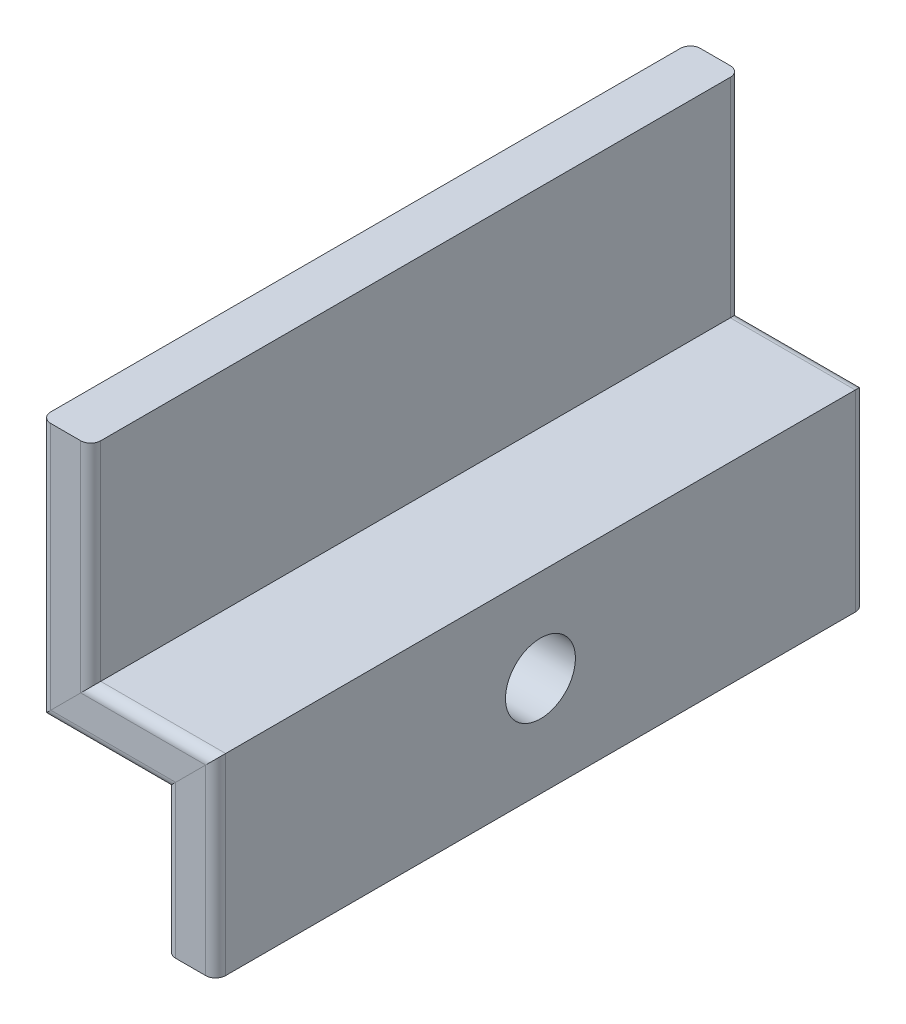
SolidWorks part; units mm, degrees
ref_plane "Front Plane" through (0, 0, 0) normal (0, 0, 1) x (1, 0, 0)
ref_plane "Top Plane" through (0, 0, 0) normal (0, 1, 0) x (1, 0, 0)
ref_plane "Right Plane" through (0, 0, 0) normal (1, 0, 0) x (0, 0, -1)
sketch3d "3DSketch1"
  line L0 (0, 0, 0) -> (0, 33.5, 0)
  line L1 (0, 33.5, 0) -> (-25, 33.5, 0)
  line L2 (-25, 33.5, 0) -> (-25, 80.2, 0)
  line L3 (-25, 80.2, 0) -> (39.395, 80.2, 0) construction
  dimension "D1" = 25
  dimension "D2" = 46.7
  dimension "D3" = 33.5
sketch "Sketch2" plane through (0, 0, 0) normal (0, 1, 0) x (1, 0, 0)
  line L1 (-3, 65) -> (3, 65)
  line L2 (-5, 63) -> (-5, -63)
  line L3 (-3, -65) -> (3, -65)
  line L4 (5, 63) -> (5, -63)
  line L5 (-5, 65) -> (5, -65) construction
  line L6 (-5, -65) -> (5, 65) construction
  arc A0 (3, 65) -> (5, 63) centre (3, 63) cw
  arc A1 (5, -63) -> (3, -65) centre (3, -63) cw
  arc A2 (-3, -65) -> (-5, -63) centre (-3, -63) cw
  arc A3 (-5, 63) -> (-3, 65) centre (-3, 63) cw
  point P0 (0, 0)
  dimension "D3" = 2
  dimension "D1" = 130
  dimension "D2" = 10
sketch "Sketch3" plane through (0, 0, 0) normal (1, 0, 0) x (0, 0, -1)
  line L0 (0, 0) -> (0, 33.5) construction
  circle A0 centre (0, 20) radius 7
  dimension "D1" = 14
  dimension "D2" = 20
sweep "Sweep1" add profiles "Sketch2" path "3DSketch1"
extrude "Cut-Extrude1" cut sketch "Sketch3" against normal through all both and the other way through all
